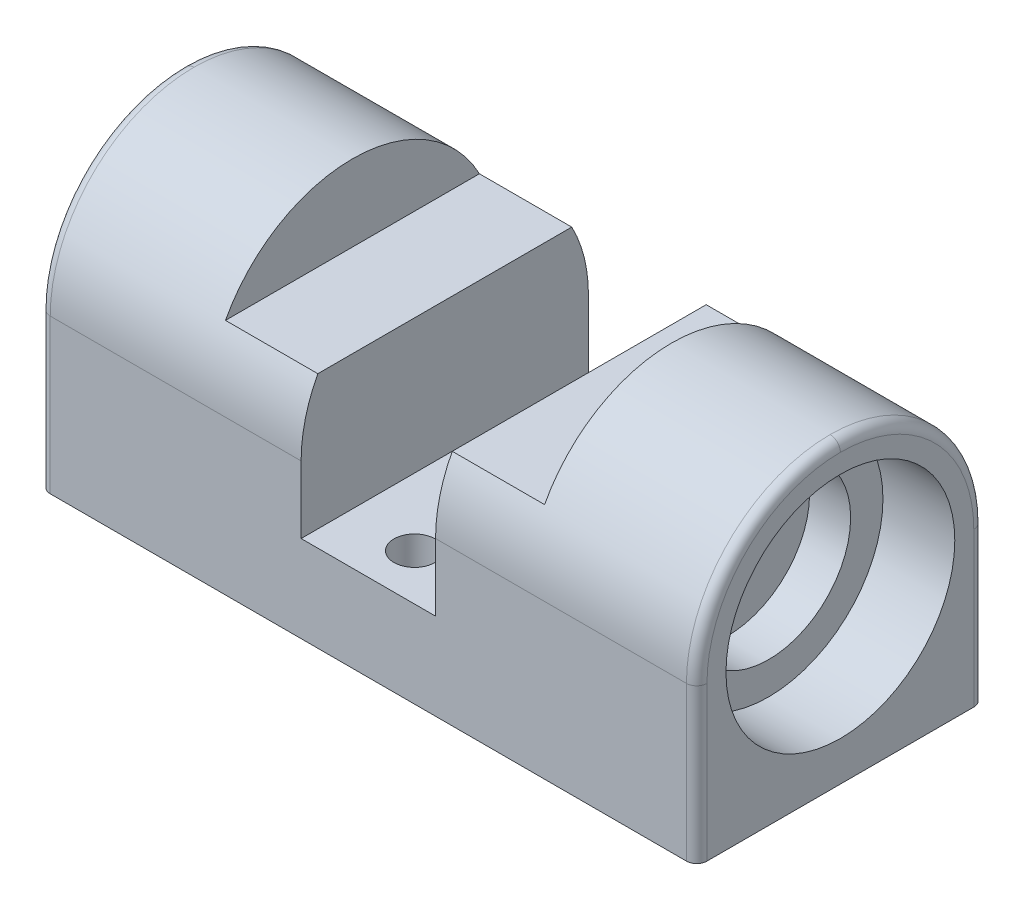
SolidWorks part; units mm, degrees
ref_plane "Front Plane" through (0, 0, 0) normal (0, 0, 1) x (1, 0, 0)
ref_plane "Top Plane" through (0, 0, 0) normal (0, 1, 0) x (1, 0, 0)
ref_plane "Right Plane" through (0, 0, 0) normal (1, 0, 0) x (0, 0, -1)
sketch "Sketch1" plane through (0, 0, 0) normal (0, 1, 0) x (1, 0, 0)
  circle A0 centre (0, 0) radius 21.25
  circle A1 centre (0, 0) radius 26
  dimension "D1" = 42.5
  dimension "D2" = 52
extrude "Boss-Extrude1" add sketch "Sketch1" along normal blind 9
sketch "Sketch2" plane through (0, 0, 0) normal (0, -1, 0) x (1, 0, 0)
  circle A0 centre (0, 0) radius 21.25
  circle A1 centre (0, 0) radius 26 construction
  circle A2 centre (0, 0) radius 26
  circle A3 centre (0, 0) radius 21.25 construction
extrude "Boss-Extrude2" add sketch "Sketch2" along normal blind 2
sketch "Sketch3" plane through (0, 9, 0) normal (0, 1, 0) x (1, 0, 0)
  line L0 (0, 0) -> (26.625, 0) construction
  line L1 (0, 0) -> (-26.625, 0) construction
  line L3 (21.25, 14) -> (32, 14)
  line L4 (21.25, 14) -> (21.25, -14)
  line L5 (21.25, -14) -> (32, -14)
  line L6 (32, 14) -> (32, -14)
  line L7 (21.25, 14) -> (32, -14) construction
  line L8 (21.25, -14) -> (32, 14) construction
  line L9 (-32, 14) -> (-21.25, 14)
  line L10 (-32, 14) -> (-32, -14)
  line L11 (-32, -14) -> (-21.25, -14)
  line L12 (-21.25, 14) -> (-21.25, -14)
  line L13 (-32, 14) -> (-21.25, -14) construction
  line L14 (-32, -14) -> (-21.25, 14) construction
  circle A1 centre (0, 0) radius 21.25 construction
  dimension "D1" = 28
  dimension "D2" = 32
extrude "Boss-Extrude3" add sketch "Sketch3" against normal up to surface (11 mm away) and the other way blind 18 up to face at (0, -2, -26)
sketch "Sketch4" plane through (32, 0, 0) normal (1, 0, 0) x (0, 0, -1)
  line L0 (0, -2) -> (0, 13) construction
  line L1 (-14, -2) -> (14, -2) construction
  circle A0 centre (0, 13) radius 11.15
  dimension "D1" = 22.3
  dimension "D2" = 15
extrude "Cut-Extrude1" cut sketch "Sketch4" against normal blind 7 contours A0
sketch "Sketch5" plane through (-32, 0, 0) normal (-1, 0, 0) x (0, 0, 1)
  circle A0 centre (0, 13) radius 11.15 construction
  circle A1 centre (0, 13) radius 11.15
extrude "Cut-Extrude2" cut sketch "Sketch5" against normal blind 7
fillet "Fillet2" radius 14 4 edges at (-26.625, 27, 14) (-26.625, 27, -14) (26.625, 27, -14) (26.625, 27, 14)
fillet "Fillet4" radius 1 8 edges at (-32, 5.5, -14) (-32, 22.8995, -9.8995) (-32, 22.8995, 9.8995) (32, 5.5, -14) (32, 22.8995, -9.8995) (32, 22.8995, 9.8995) (-32, 5.5, 14) (32, 5.5, 14)
sketch "Sketch8" plane through (0, -2, 0) normal (0, -1, 0) x (1, 0, 0)
  line L1 (-21.9089, -14) -> (21.9089, -14)
  line L2 (-21.9089, -14) -> (-21.9089, 14)
  line L3 (-21.9089, 14) -> (21.9089, 14)
  line L4 (21.9089, -14) -> (21.9089, 14)
extrude "Boss-Extrude4" add sketch "Sketch8" against normal up to surface (11 mm away) up to face at (0, 9, 14.875)
sketch "Sketch9" plane through (0, 9, 0) normal (0, 1, 0) x (1, 0, 0)
  line L1 (21.9089, 14) -> (-21.9089, 14)
  line L2 (21.9089, 14) -> (21.9089, 26)
  line L3 (21.9089, 26) -> (-21.9089, 26)
  line L4 (-21.9089, 14) -> (-21.9089, 26)
  line L5 (-21.9089, -14) -> (21.9089, -14)
  line L6 (-21.9089, -14) -> (-21.9089, -26)
  line L7 (-21.9089, -26) -> (21.9089, -26)
  line L8 (21.9089, -14) -> (21.9089, -26)
  arc A0 (-21.9089, -14) -> (21.9089, -14) centre (0, 0) ccw construction
  arc A1 (21.9089, 14) -> (-21.9089, 14) centre (0, 0) ccw construction
extrude "Cut-Extrude4" cut sketch "Sketch9" against normal through all
sketch "Sketch12" plane through (21.25, 0, 0) normal (-1, 0, 0) x (0, 0, 1)
  line L3 (-14, 13) -> (-14, 9)
  line L4 (-14, 9) -> (14, 9)
  line L5 (14, 9) -> (14, 13)
  line L6 (-14, 13) -> (-14, 9)
  line L7 (-14, 9) -> (14, 9)
  line L8 (14, 9) -> (14, 13)
  arc A2 (14, 13) -> (0, 27) centre (0, 13) ccw
  arc A3 (0, 27) -> (-14, 13) centre (0, 13) ccw
  arc A4 (14, 13) -> (0, 27) centre (0, 13) ccw
  arc A5 (0, 27) -> (-14, 13) centre (0, 13) ccw
  dimension "D1" = 0
extrude "Boss-Extrude5" add sketch "Sketch12" along normal up to surface (42.5 mm away) up to face at (-21.25, 15.3598, 0)
sketch "Sketch6" plane through (25, 0, 0) normal (1, 0, 0) x (0, 0, -1)
  circle A0 centre (0, 13) radius 8
  circle A1 centre (0, 13) radius 11.15 construction
  dimension "D1" = 16
extrude "Cut-Extrude3" cut sketch "Sketch6" against normal through all
sketch "Sketch14" plane through (25, 0, 0) normal (1, 0, 0) x (0, 0, -1)
  line L0 (-14, -2) -> (-14, 13) construction
  line L1 (14, 13) -> (14, -2) construction
  line L2 (-14, -2) -> (-14, 13)
  line L3 (14, 13) -> (14, -2)
  line L4 (-14, -2) -> (14, -2)
  arc A0 (0, 27) -> (-14, 13) centre (0, 13) ccw construction
  arc A1 (14, 13) -> (0, 27) centre (0, 13) ccw construction
  arc A2 (0, 27) -> (-14, 13) centre (0, 13) ccw
  arc A3 (14, 13) -> (0, 27) centre (0, 13) ccw
extrude "Boss-Extrude6" add sketch "Sketch14" against normal offset from surface (42 mm away) 4 from offset 4 up to face at (-25, 13, 8) offset against normal yes
sketch "Sketch11" plane through (0, -2, 0) normal (0, -1, 0) x (1, 0, 0)
  line L0 (0, -14) -> (0, 14) construction
  line L1 (31, -14) -> (-31, -14) construction
  line L2 (-31, 14) -> (31, 14) construction
  circle A0 centre (0, -9.5) radius 2
  circle A1 centre (0, 9.5) radius 2
  circle A2 centre (0, 0) radius 2
  dimension "D1" = 4
  dimension "D2" = 9.5
  dimension "D3" = 9.5
extrude "Cut-Extrude5" cut sketch "Sketch11" against normal through all
sketch "Sketch13" plane through (0, 0, -14) normal (0, 0, -1) x (-1, 0, 0)
  line L0 (0, -2) -> (0, 19.55) construction
  line L1 (-31, -2) -> (31, -2) construction
  line L2 (0, 19.55) -> (15.5472, 19.55)
  line L3 (0, 19.55) -> (-15.5472, 19.55)
  line L4 (-15.5472, 19.55) -> (-15.5472, 33.0629)
  line L5 (-15.5472, 33.0629) -> (15.5472, 33.0629)
  line L6 (15.5472, 33.0629) -> (15.5472, 19.55)
  line L7 (31, 13) -> (-31, 13) construction
  line L8 (-6.55, 6.45) -> (6.55, 6.45)
  line L9 (-6.55, 6.45) -> (-6.55, 19.55)
  line L10 (-6.55, 19.55) -> (6.55, 19.55)
  line L11 (6.55, 6.45) -> (6.55, 19.55)
  line L12 (-6.55, 6.45) -> (6.55, 19.55) construction
  line L13 (-6.55, 19.55) -> (6.55, 6.45) construction
  point P5 (0, 13)
  line M7 (31, 13) -> (-31, 13)
  dimension "D1" = 13.1
  dimension "D2" = 13.1
extrude "Cut-Extrude6" cut sketch "Sketch13" against normal through all contours L6 L5 L4 L3 L2 | L11 L2 L3 L9 M7 | L8 L11 L9 M7 region at (0, 26.3064, -14) region at (0, 16.275, -14) region at (0, 9.725, -14)
